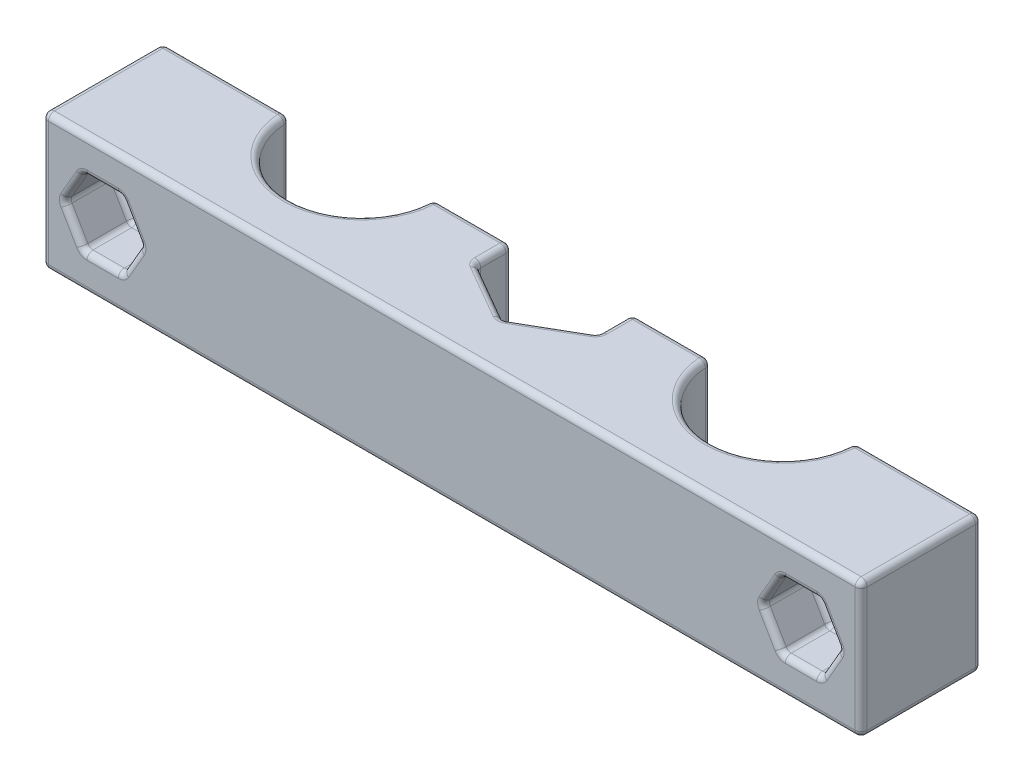
SolidWorks part; units mm, degrees
ref_plane "Front Plane" through (0, 0, 0) normal (0, 0, 1) x (1, 0, 0)
ref_plane "Top Plane" through (0, 0, 0) normal (0, 1, 0) x (1, 0, 0)
ref_plane "Right Plane" through (0, 0, 0) normal (1, 0, 0) x (0, 0, -1)
sketch "Sketch1" plane through (0, 0, 0) normal (0, 1, 0) x (1, 0, 0)
  line L0 (34, 0) -> (34, 10) construction
  line L1 (0, 0) -> (68, 0) construction
  line L2 (0, 0) -> (0, 10) construction
  line L3 (0, 10) -> (68, 10) construction
  line L4 (68, 0) -> (68, 10) construction
  line L5 (34, 4.2265) -> (39, 7.1132) construction
  line L6 (39, 7.1132) -> (39, 12.8868) construction
  line L7 (39, 12.8868) -> (34, 15.7735) construction
  line L8 (34, 15.7735) -> (29, 12.8868) construction
  line L9 (29, 12.8868) -> (29, 7.1132) construction
  line L10 (29, 7.1132) -> (34, 4.2265) construction
  line L11 (57.5, 10) -> (68, 10)
  line L12 (68, 10) -> (68, 0)
  line L13 (68, 0) -> (0, 0)
  line L14 (0, 0) -> (0, 10)
  line L15 (0, 10) -> (10.5, 10)
  line L16 (22.5, 10) -> (29, 10)
  line L21 (39, 10) -> (45.5, 10)
  line L22 (29, 10) -> (29, 7.1132)
  line L23 (29, 7.1132) -> (34, 4.2265)
  line L24 (34, 4.2265) -> (39, 7.1132)
  line L25 (39, 7.1132) -> (39, 10)
  circle A0 centre (34, 10) radius 5 construction
  circle A1 centre (16.5, 10) radius 6 construction
  circle A2 centre (51.5, 10) radius 6 construction
  arc A3 (10.5, 10) -> (22.5, 10) centre (16.5, 10) ccw
  arc A4 (45.5, 10) -> (57.5, 10) centre (51.5, 10) ccw
  dimension "D4" = 12
  dimension "D1" = 10
  dimension "D2" = 10
  dimension "D3" = 68
  dimension "D5" = 17.5
extrude "Boss-Extrude1" add sketch "Sketch1" along normal blind 11.3
sketch "Sketch2" plane through (0, 0, 0) normal (0, 0, 1) x (1, 0, 0)
  line L0 (34, 11.3) -> (34, 0) construction
  line L1 (0, 0) -> (68, 0) construction
  line L2 (0, 5.65) -> (5, 5.65) construction
  line L3 (0, 11.3) -> (0, 0) construction
  circle A0 centre (5, 5.65) radius 1.6
  circle A1 centre (63, 5.65) radius 1.6
  point P12 (34, 5.65)
  dimension "D2" = 3.2
  dimension "D1" = 29
extrude "Cut-Extrude1" cut sketch "Sketch2" against normal through all
sketch "Sketch4" plane through (0, 0, 0) normal (0, 0, 1) x (1, 0, 0)
  line L0 (34, 11.3) -> (34, 0) construction
  line L1 (8.1754, 5.65) -> (6.5877, 8.4)
  line L2 (6.5877, 8.4) -> (3.4123, 8.4)
  line L3 (3.4123, 8.4) -> (1.8246, 5.65)
  line L4 (1.8246, 5.65) -> (3.4123, 2.9)
  line L5 (3.4123, 2.9) -> (6.5877, 2.9)
  line L6 (6.5877, 2.9) -> (8.1754, 5.65)
  line L7 (0, 11.3) -> (68, 11.3) construction
  line L8 (61.4123, 2.9) -> (59.8246, 5.65)
  line L9 (64.5877, 2.9) -> (61.4123, 2.9)
  line L10 (66.1754, 5.65) -> (64.5877, 2.9)
  line L11 (64.5877, 8.4) -> (66.1754, 5.65)
  line L12 (61.4123, 8.4) -> (64.5877, 8.4)
  line L13 (59.8246, 5.65) -> (61.4123, 8.4)
  circle A0 centre (5, 5.65) radius 2.75 construction
  circle A1 centre (5, 5.65) radius 1.6 construction
  dimension "D1" = 5.5
extrude "Cut-Extrude3" cut sketch "Sketch4" against normal blind 4.2
fillet "Fillet5" radius 0.5 79 edges at (61.4123, 8.4, -2.1) (59.8246, 5.65, -2.1) (61.4123, 2.9, -2.1) (64.5877, 2.9, -2.1) (66.1754, 5.65, -2.1) (64.5877, 8.4, -2.1) (61.4, 5.65, -4.2) (60.6184, 4.275, -4.2) (60.6184, 7.025, -4.2) (63, 8.4, -4.2) (65.3816, 7.025, -4.2) (65.3816, 4.275, -4.2) (63, 2.9, -4.2) (6.5877, 2.9, -2.1) (8.1754, 5.65, -2.1) (1.8246, 5.65, -2.1) (3.4123, 2.9, -2.1) (6.5877, 8.4, -2.1) (3.4123, 8.4, -2.1) (6.6, 5.65, -4.2) (5, 2.9, -4.2) (2.6184, 4.275, -4.2) (2.6184, 7.025, -4.2) (5, 8.4, -4.2) (7.3816, 7.025, -4.2) (7.3816, 4.275, -4.2) (68, 0, -5) (39, 0, -8.5566) (29, 0, -8.5566) (0, 0, -5) (68, 5.65, -10) (62.75, 0, -10) (61.4, 5.65, -10) (57.5, 5.65, -10) (51.5, 0, -4) (45.5, 5.65, -10) (39, 5.65, -10) (42.25, 0, -10) (39, 5.65, -7.1132) (36.5, 0, -5.6699) (34, 5.65, -4.2265) (29, 5.65, -7.1132) (31.5, 0, -5.6699) (29, 5.65, -10) (25.75, 0, -10) (22.5, 5.65, -10) (16.5, 0, -4) (10.5, 5.65, -10) (0, 5.65, -10) (5.25, 0, -10) (6.6, 5.65, -10) (5.25, 11.3, -10) (16.5, 11.3, -4) (25.75, 11.3, -10) (29, 11.3, -8.5566) (31.5, 11.3, -5.6699) (36.5, 11.3, -5.6699) (39, 11.3, -8.5566) (42.25, 11.3, -10) (51.5, 11.3, -4) (62.75, 11.3, -10) (68, 11.3, -5) (0, 11.3, -5) (0, 5.65, 0) (34, 11.3, 0) (68, 5.65, 0) (34, 0, 0) (65.3816, 7.025, 0) (63, 8.4, 0) (60.6184, 7.025, 0) (60.6184, 4.275, 0) (63, 2.9, 0) (65.3816, 4.275, 0) (5, 8.4, 0) (2.6184, 7.025, 0) (2.6184, 4.275, 0) (5, 2.9, 0) (7.3816, 4.275, 0) (7.3816, 7.025, 0)
